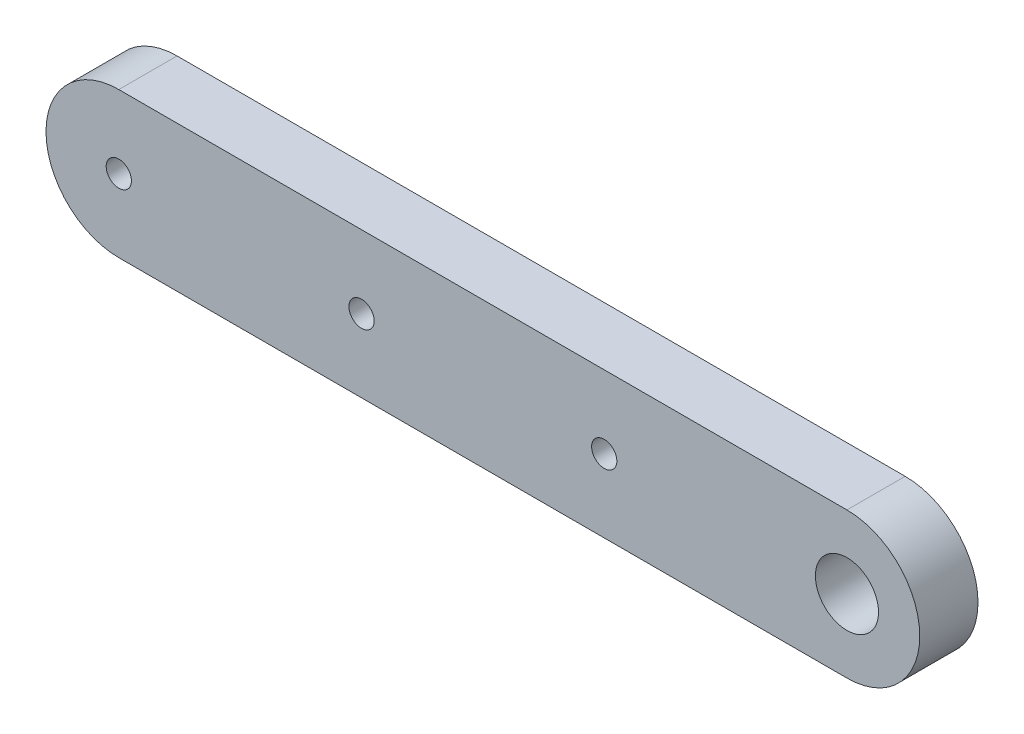
SolidWorks part; units mm, degrees
material "Pine"
ref_plane "Front Plane" through (0, 0, 0) normal (0, 0, 1) x (1, 0, 0)
ref_plane "Top Plane" through (0, 0, 0) normal (0, 1, 0) x (1, 0, 0)
ref_plane "Right Plane" through (0, 0, 0) normal (1, 0, 0) x (0, 0, -1)
sketch "Sketch1" plane through (0, 0, 0) normal (0, 0, 1) x (1, 0, 0)
  line L0 (0, 7.5) -> (75, 7.5)
  line L1 (75, -7.5) -> (0, -7.5)
  circle A0 centre (0, 0) radius 7.5
  circle A1 centre (75, 0) radius 7.5
  dimension "D1" = 75
  dimension "D2" = 15
extrude "Boss-Extrude1" add sketch "Sketch1" along normal blind 6 contours A1 L0 A0 L1 | A1 | A0 region at (37.5, 0, 0) region at (0, 0, 0) region at (75, 0, 0)
ref_plane "Plane1" through (0, 0, 3) normal (0, 0, 1) x (1, 0, 0)
sketch "Sketch2" plane through (0, 0, 6) normal (0, 0, 1) x (1, 0, 0)
  circle A0 centre (0, 0) radius 1.3
  circle A1 centre (75, 0) radius 1.3
  dimension "D1" = 2.6
extrude "Cut-Extrude1" cut sketch "Sketch2" against normal through all
pattern_linear "LPattern1" count 4 spacing 25 along (1, 0, 0) of "Cut-Extrude1"
sketch "Sketch3" plane through (0, 0, 6) normal (0, 0, 1) x (1, 0, 0)
  circle A0 centre (75, 0) radius 3.25
  dimension "D1" = 6.5
extrude "Cut-Extrude2" cut sketch "Sketch3" against normal through all
